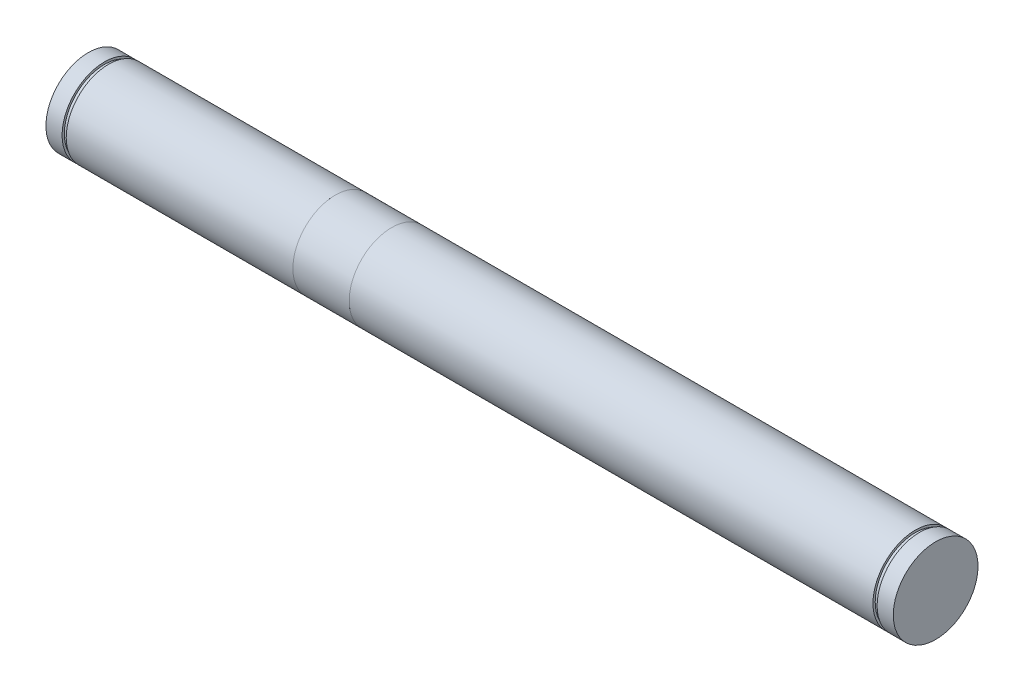
SolidWorks part; units mm, degrees
material "1.7225 (42CrMo4)"
ref_plane "E_Oben" through (0, 0, 0) normal (0, 0, 1) x (1, 0, 0)
ref_plane "E_Vorne" through (0, 0, 0) normal (0, 1, 0) x (1, 0, 0)
ref_plane "E_Rechts" through (0, 0, 0) normal (1, 0, 0) x (0, 0, -1)
ref_axis "A_Drehachse" through (-88.99, 0, 0) along (1, 0, 0)
sketch "Skizze1" plane through (0, 0, 0) normal (0, 0, 1) x (1, 0, 0)
  line L1 (0, -55) -> (0, 55) construction
  line L3 (190, 19) -> (190, 0)
  line L4 (190, 0) -> (-190, 0)
  line L5 (-54, 19.001) -> (-54, 19)
  line L6 (-54, 19.001) -> (-84, 19.001)
  line L7 (-190, 19) -> (-190, 0)
  line L10 (-89, 19) -> (-89, 27)
  line L11 (-89, 27) -> (-84, 27)
  line L12 (-84, 27) -> (-84, 19.001)
  line L14 (-190, 19) -> (-89, 19)
  line L17 (-54, 19) -> (190, 19)
  point P12 (0, 0)
  dimension "D1" = 101
  dimension "D2" = 19
  dimension "D3" = 19.001
  dimension "D4" = 190
  dimension "D5" = 27
  dimension "D6" = 30
  dimension "D7" = 5
revolve "Rotation1" add sketch "Skizze1" angle 360 about L4
sketch "Skizze19" plane through (0, 0, 0) normal (0, 0, 1) x (1, 0, 0)
  line L5 (-88.99, 0) -> (88.99, 0) construction
  line L8 (180.9, 19) -> (182.75, 19)
  line L9 (180.9, 19) -> (180.9, 18)
  line L10 (180.9, 18) -> (182.75, 18)
  line L11 (182.75, 19) -> (182.75, 18)
  line L14 (190, 19) -> (-54, 19) construction
  line L15 (190, -19) -> (190, 19) construction
  dimension "D1" = 7.25
  dimension "D2" = 0
  dimension "D4" = 1.85
  dimension "D5" = 18
revolve "Schnitt-Rotation1" cut sketch "Skizze19" angle 360 about axis through (-88.99, 0, 0) along (1, 0, 0)
sketch "Skizze20" plane through (0, 0, 0) normal (0, 0, 1) x (1, 0, 0)
  line L1 (-182.75, 19) -> (-180.9, 19)
  line L2 (-182.75, 19) -> (-182.75, 18)
  line L3 (-182.75, 18) -> (-180.9, 18)
  line L4 (-180.9, 19) -> (-180.9, 18)
  line L7 (-89, 19) -> (-190, 19) construction
  line L8 (-190, 19) -> (-190, -19) construction
  dimension "D1" = 7.25
  dimension "D2" = 1.85
  dimension "D3" = 1
  dimension "D4" = 0
revolve "Schnitt-Rotation2" cut sketch "Skizze20" angle 360 about axis through (-88.99, 0, 0) along (1, 0, 0)
sketch "Sketch1" plane through (0, 0, 0) normal (0, 0, 1) x (1, 0, 0)
  line L0 (-89, 19) -> (-180.9, 19) construction
  line L1 (-93.331, 19) -> (-79.2296, 19)
  line L2 (-93.331, 19) -> (-93.331, 30.2934)
  line L3 (-93.331, 30.2934) -> (-79.2296, 30.2934)
  line L4 (-79.2296, 19) -> (-79.2296, 30.2934)
  line L5 (-190, 19) -> (-190, -19) construction
  line L6 (-191.1647, 0) -> (203.9937, 0) construction
  dimension "D1" = 14.1014
  dimension "D2" = 11.2934
  dimension "D3" = 110.7704
revolve "Cut-Revolve1" cut sketch "Sketch1" angle 360 about L6
